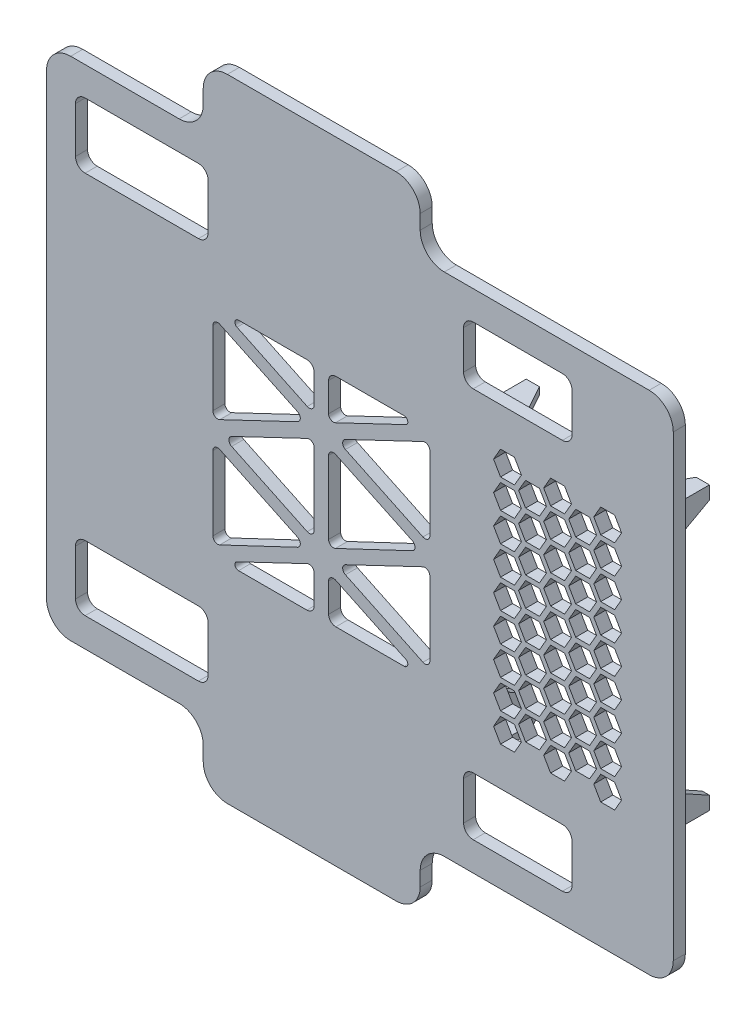
SolidWorks part; units mm, degrees
ref_plane "前视基准面" through (0, 0, 0) normal (0, 0, 1) x (1, 0, 0)
ref_plane "上视基准面" through (0, 0, 0) normal (0, 1, 0) x (1, 0, 0)
ref_plane "右视基准面" through (0, 0, 0) normal (1, 0, 0) x (0, 0, -1)
sketch "草图1" plane through (0, 0, 0) normal (0, 0, 1) x (1, 0, 0)
  line L2 (-130, 95) -> (-130, -95)
  line L3 (-120, -105) -> (-75, -105)
  line L4 (130, 95) -> (130, -95)
  line L5 (126.7518, 102.3765) -> (130, 105) construction
  line L6 (-130, -105) -> (-126.7518, -102.3765) construction
  line L9 (-65, -115) -> (-65, -121)
  line L10 (-55, -131) -> (15, -131)
  line L11 (25, -121) -> (25, -115)
  line L13 (35, -105) -> (120, -105)
  line L14 (126.7518, -102.3765) -> (130, -105) construction
  line L15 (-130, 105) -> (-126.7518, 102.3765) construction
  line L16 (-130, 0) -> (130, 0) construction
  line L17 (35, 105) -> (120, 105)
  line L18 (25, 121) -> (25, 115)
  line L19 (-55, 131) -> (15, 131)
  line L20 (-65, 115) -> (-65, 121)
  line L21 (-120, 105) -> (-75, 105)
  arc A1 (-120, -105) -> (-130, -95) centre (-120, -95) cw
  arc A3 (120, -105) -> (130, -95) centre (120, -95) ccw
  arc A8 (-65, -115) -> (-75, -105) centre (-75, -115) ccw
  arc A9 (25, -115) -> (35, -105) centre (35, -115) cw
  arc A10 (-55, -131) -> (-65, -121) centre (-55, -121) cw
  arc A11 (15, -131) -> (25, -121) centre (15, -121) ccw
  arc A12 (15, 131) -> (25, 121) centre (15, 121) cw
  arc A13 (-55, 131) -> (-65, 121) centre (-55, 121) ccw
  arc A14 (25, 115) -> (35, 105) centre (35, 115) ccw
  arc A15 (-65, 115) -> (-75, 105) centre (-75, 115) cw
  arc A16 (120, 105) -> (130, 95) centre (120, 95) cw
  arc A17 (-120, 105) -> (-130, 95) centre (-120, 95) ccw
  point P0 (0, 0)
  point P40 (25, -105)
  point P45 (25, 105)
  dimension "D2" = 10
  dimension "D3" = 65
  dimension "D4" = 10
  dimension "D5" = 105
  dimension "D7" = 10
  dimension "D8" = 10
  dimension "D10" = 10
  dimension "D12" = 10
  dimension "D13" = 105
  dimension "D18" = 90
  dimension "D19" = 6
extrude "凸台-拉伸1" add sketch "草图1" along normal blind 5
sketch "草图4" plane through (0, 0, 0) normal (0, 0, -1) x (-1, 0, 0)
  line L0 (-44, -47.5) -> (-44, -58.5)
  line L1 (-44, -58.5) -> (-55, -58.5)
  line L2 (-55, -58.5) -> (-55, -55.5)
  line L3 (-55, -55.5) -> (-47, -55.5)
  line L4 (-47, -55.5) -> (-47, -47.5)
  line L5 (-47, -47.5) -> (-44, -47.5)
  line L6 (-130, 0) -> (-25.5592, 0) construction
  line L7 (-130, -95) -> (-130, 95) construction
  line L10 (-130, -95) -> (-130, 95) construction
  dimension "D1" = 11
  dimension "D2" = 11
  dimension "D3" = 3
  dimension "D4" = 3
  dimension "D5" = 75
  dimension "D7" = 55.5
extrude "凸台-拉伸2" add sketch "草图4" along normal blind 20
sketch "草图5" plane through (0, -58.5, 0) normal (0, -1, 0) x (1, 0, 0)
  line L0 (55, -10) -> (49.5, -20)
  line L1 (55, -20) -> (55, 0) construction
  line L2 (55, -20) -> (44, -20) construction
  line L3 (49.5, -20) -> (55, -20)
  line L4 (55, -20) -> (55, -10)
  dimension "D1" = 10
  dimension "D2" = 5.5
extrude "切除-拉伸3" cut sketch "草图5" against normal blind 10
sketch "草图6" plane through (44, 0, 0) normal (-1, 0, 0) x (0, 0, 1)
  line L0 (-20, -53) -> (-10, -47.5)
  line L1 (-20, -58.5) -> (-20, -47.5) construction
  line L2 (-20, -47.5) -> (0, -47.5) construction
  line L3 (-10, -47.5) -> (-20, -47.5)
  line L4 (-20, -47.5) -> (-20, -53)
  dimension "D1" = 10
  dimension "D2" = 5.5
extrude "切除-拉伸4" cut sketch "草图6" against normal blind 10
ref_plane "基准面2" through (82, 0, 0) normal (1, 0, 0) x (0, 0, -1)
mirror "镜向1" about plane through (82, 0, 0) normal (1, 0, 0) of "凸台-拉伸2", "切除-拉伸4", "切除-拉伸3"
mirror "镜向2" about plane through (0, 0, 0) normal (0, 1, 0) of "镜向1"
sketch "草图7" plane through (0, 0, 0) normal (0, 0, -1) x (-1, 0, 0)
  line L4 (-117, -55.5) -> (-109, -55.5) construction
  line L5 (-117, 47.5) -> (-117, 55.5) construction
  line L6 (-117, 55.5) -> (-109, 55.5) construction
  line L7 (-97.013, 36) -> (-99.8997, 41)
  line L8 (-99.8997, 41) -> (-105.6732, 41)
  line L9 (-105.6732, 41) -> (-108.56, 36)
  line L10 (-108.56, 36) -> (-105.6732, 31)
  line L11 (-105.6732, 31) -> (-99.8997, 31)
  line L12 (-99.8997, 31) -> (-97.013, 36)
  line L13 (-82.0019, 36) -> (-102.7865, 36) construction
  line L14 (-79.1151, 31) -> (-76.2284, 36)
  line L15 (-76.2284, 36) -> (-79.1151, 41)
  line L16 (-79.1151, 41) -> (-84.8886, 41)
  line L17 (-84.8886, 41) -> (-87.7754, 36)
  line L18 (-87.7754, 36) -> (-84.8886, 31)
  line L19 (-84.8886, 31) -> (-79.1151, 31)
  line L20 (-97.013, 24) -> (-99.8997, 29)
  line L21 (-98.1677, 30) -> (-95.2809, 25)
  line L22 (-95.2809, 25) -> (-89.5074, 25)
  line L23 (-89.5074, 25) -> (-86.6207, 30)
  line L24 (-86.6207, 30) -> (-89.5074, 35)
  line L25 (-89.5074, 35) -> (-95.2809, 35)
  line L26 (-95.2809, 35) -> (-98.1677, 30)
  line L27 (-89.5074, 37) -> (-86.6207, 42)
  line L28 (-86.6207, 42) -> (-89.5074, 47)
  line L29 (-89.5074, 47) -> (-95.2809, 47)
  line L30 (-95.2809, 47) -> (-98.1677, 42)
  line L31 (-98.1677, 42) -> (-95.2809, 37)
  line L32 (-95.2809, 37) -> (-89.5074, 37)
  line L33 (-84.8886, 43) -> (-79.1151, 43)
  line L34 (-79.1151, 43) -> (-76.2284, 48)
  line L35 (-76.2284, 48) -> (-79.1151, 53)
  line L36 (-79.1151, 53) -> (-84.8886, 53)
  line L37 (-84.8886, 53) -> (-87.7754, 48)
  line L38 (-87.7754, 48) -> (-84.8886, 43)
  line L39 (-99.8997, 43) -> (-97.013, 48)
  line L40 (-97.013, 48) -> (-99.8997, 53)
  line L41 (-99.8997, 53) -> (-105.6732, 53)
  line L42 (-105.6732, 53) -> (-108.56, 48)
  line L43 (-108.56, 48) -> (-105.6732, 43)
  line L44 (-105.6732, 43) -> (-99.8997, 43)
  line L45 (-77.3831, 42) -> (-74.4963, 37)
  line L46 (-74.4963, 37) -> (-68.7228, 37)
  line L47 (-68.7228, 37) -> (-65.8361, 42)
  line L48 (-65.8361, 42) -> (-68.7228, 47)
  line L49 (-68.7228, 47) -> (-74.4963, 47)
  line L50 (-74.4963, 47) -> (-77.3831, 42)
  line L51 (-99.8997, 29) -> (-105.6732, 29)
  line L52 (-105.6732, 29) -> (-108.56, 24)
  line L53 (-108.56, 24) -> (-105.6732, 19)
  line L54 (-105.6732, 19) -> (-99.8997, 19)
  line L55 (-99.8997, 19) -> (-97.013, 24)
  line L56 (-98.1677, 18) -> (-95.2809, 13)
  line L57 (-95.2809, 13) -> (-89.5074, 13)
  line L58 (-89.5074, 13) -> (-86.6207, 18)
  line L59 (-86.6207, 18) -> (-89.5074, 23)
  line L60 (-89.5074, 23) -> (-95.2809, 23)
  line L61 (-95.2809, 23) -> (-98.1677, 18)
  line L62 (-79.1151, 19) -> (-76.2284, 24)
  line L63 (-76.2284, 24) -> (-79.1151, 29)
  line L64 (-79.1151, 29) -> (-84.8886, 29)
  line L65 (-84.8886, 29) -> (-87.7754, 24)
  line L66 (-87.7754, 24) -> (-84.8886, 19)
  line L67 (-84.8886, 19) -> (-79.1151, 19)
  line L68 (-77.3831, 30) -> (-74.4963, 25)
  line L69 (-74.4963, 25) -> (-68.7228, 25)
  line L70 (-68.7228, 25) -> (-65.8361, 30)
  line L71 (-65.8361, 30) -> (-68.7228, 35)
  line L72 (-68.7228, 35) -> (-74.4963, 35)
  line L73 (-74.4963, 35) -> (-77.3831, 30)
  line L74 (-97.013, 12) -> (-99.8997, 17)
  line L75 (-99.8997, 17) -> (-105.6732, 17)
  line L76 (-105.6732, 17) -> (-108.56, 12)
  line L77 (-108.56, 12) -> (-105.6732, 7)
  line L78 (-105.6732, 7) -> (-99.8997, 7)
  line L79 (-99.8997, 7) -> (-97.013, 12)
  line L80 (-98.1677, 6) -> (-95.2809, 1)
  line L81 (-95.2809, 1) -> (-89.5074, 1)
  line L82 (-89.5074, 1) -> (-86.6207, 6)
  line L83 (-86.6207, 6) -> (-89.5074, 11)
  line L84 (-89.5074, 11) -> (-95.2809, 11)
  line L85 (-95.2809, 11) -> (-98.1677, 6)
  line L86 (-79.1151, 7) -> (-76.2284, 12)
  line L87 (-76.2284, 12) -> (-79.1151, 17)
  line L88 (-79.1151, 17) -> (-84.8886, 17)
  line L89 (-84.8886, 17) -> (-87.7754, 12)
  line L90 (-87.7754, 12) -> (-84.8886, 7)
  line L91 (-84.8886, 7) -> (-79.1151, 7)
  line L92 (-77.3831, 18) -> (-74.4963, 13)
  line L93 (-74.4963, 13) -> (-68.7228, 13)
  line L94 (-68.7228, 13) -> (-65.8361, 18)
  line L95 (-65.8361, 18) -> (-68.7228, 23)
  line L96 (-68.7228, 23) -> (-74.4963, 23)
  line L97 (-74.4963, 23) -> (-77.3831, 18)
  line L98 (-97.013, 0) -> (-99.8997, 5)
  line L99 (-99.8997, 5) -> (-105.6732, 5)
  line L100 (-105.6732, 5) -> (-108.56, 0)
  line L101 (-108.56, 0) -> (-105.6732, -5)
  line L102 (-105.6732, -5) -> (-99.8997, -5)
  line L103 (-99.8997, -5) -> (-97.013, 0)
  line L104 (-98.1677, -6) -> (-95.2809, -11)
  line L105 (-95.2809, -11) -> (-89.5074, -11)
  line L106 (-89.5074, -11) -> (-86.6207, -6)
  line L107 (-86.6207, -6) -> (-89.5074, -1)
  line L108 (-89.5074, -1) -> (-95.2809, -1)
  line L109 (-95.2809, -1) -> (-98.1677, -6)
  line L110 (-79.1151, -5) -> (-76.2284, 0)
  line L111 (-76.2284, 0) -> (-79.1151, 5)
  line L112 (-79.1151, 5) -> (-84.8886, 5)
  line L113 (-84.8886, 5) -> (-87.7754, 0)
  line L114 (-87.7754, 0) -> (-84.8886, -5)
  line L115 (-84.8886, -5) -> (-79.1151, -5)
  line L116 (-77.3831, 6) -> (-74.4963, 1)
  line L117 (-74.4963, 1) -> (-68.7228, 1)
  line L118 (-68.7228, 1) -> (-65.8361, 6)
  line L119 (-65.8361, 6) -> (-68.7228, 11)
  line L120 (-68.7228, 11) -> (-74.4963, 11)
  line L121 (-74.4963, 11) -> (-77.3831, 6)
  line L122 (-97.013, -12) -> (-99.8997, -7)
  line L123 (-99.8997, -7) -> (-105.6732, -7)
  line L124 (-105.6732, -7) -> (-108.56, -12)
  line L125 (-108.56, -12) -> (-105.6732, -17)
  line L126 (-105.6732, -17) -> (-99.8997, -17)
  line L127 (-99.8997, -17) -> (-97.013, -12)
  line L128 (-98.1677, -18) -> (-95.2809, -23)
  line L129 (-95.2809, -23) -> (-89.5074, -23)
  line L130 (-89.5074, -23) -> (-86.6207, -18)
  line L131 (-86.6207, -18) -> (-89.5074, -13)
  line L132 (-89.5074, -13) -> (-95.2809, -13)
  line L133 (-95.2809, -13) -> (-98.1677, -18)
  line L134 (-79.1151, -17) -> (-76.2284, -12)
  line L135 (-76.2284, -12) -> (-79.1151, -7)
  line L136 (-79.1151, -7) -> (-84.8886, -7)
  line L137 (-84.8886, -7) -> (-87.7754, -12)
  line L138 (-87.7754, -12) -> (-84.8886, -17)
  line L139 (-84.8886, -17) -> (-79.1151, -17)
  line L140 (-77.3831, -6) -> (-74.4963, -11)
  line L141 (-74.4963, -11) -> (-68.7228, -11)
  line L142 (-68.7228, -11) -> (-65.8361, -6)
  line L143 (-65.8361, -6) -> (-68.7228, -1)
  line L144 (-68.7228, -1) -> (-74.4963, -1)
  line L145 (-74.4963, -1) -> (-77.3831, -6)
  line L146 (-97.013, -24) -> (-99.8997, -19)
  line L147 (-99.8997, -19) -> (-105.6732, -19)
  line L148 (-105.6732, -19) -> (-108.56, -24)
  line L149 (-108.56, -24) -> (-105.6732, -29)
  line L150 (-105.6732, -29) -> (-99.8997, -29)
  line L151 (-99.8997, -29) -> (-97.013, -24)
  line L152 (-98.1677, -30) -> (-95.2809, -35)
  line L153 (-95.2809, -35) -> (-89.5074, -35)
  line L154 (-89.5074, -35) -> (-86.6207, -30)
  line L155 (-86.6207, -30) -> (-89.5074, -25)
  line L156 (-89.5074, -25) -> (-95.2809, -25)
  line L157 (-95.2809, -25) -> (-98.1677, -30)
  line L158 (-79.1151, -29) -> (-76.2284, -24)
  line L159 (-76.2284, -24) -> (-79.1151, -19)
  line L160 (-79.1151, -19) -> (-84.8886, -19)
  line L161 (-84.8886, -19) -> (-87.7754, -24)
  line L162 (-87.7754, -24) -> (-84.8886, -29)
  line L163 (-84.8886, -29) -> (-79.1151, -29)
  line L164 (-77.3831, -18) -> (-74.4963, -23)
  line L165 (-74.4963, -23) -> (-68.7228, -23)
  line L166 (-68.7228, -23) -> (-65.8361, -18)
  line L167 (-65.8361, -18) -> (-68.7228, -13)
  line L168 (-68.7228, -13) -> (-74.4963, -13)
  line L169 (-74.4963, -13) -> (-77.3831, -18)
  line L170 (-97.013, -36) -> (-99.8997, -31)
  line L171 (-99.8997, -31) -> (-105.6732, -31)
  line L172 (-105.6732, -31) -> (-108.56, -36)
  line L173 (-108.56, -36) -> (-105.6732, -41)
  line L174 (-105.6732, -41) -> (-99.8997, -41)
  line L175 (-99.8997, -41) -> (-97.013, -36)
  line L176 (-98.1677, -42) -> (-95.2809, -47)
  line L177 (-95.2809, -47) -> (-89.5074, -47)
  line L178 (-89.5074, -47) -> (-86.6207, -42)
  line L179 (-86.6207, -42) -> (-89.5074, -37)
  line L180 (-89.5074, -37) -> (-95.2809, -37)
  line L181 (-95.2809, -37) -> (-98.1677, -42)
  line L182 (-79.1151, -41) -> (-76.2284, -36)
  line L183 (-76.2284, -36) -> (-79.1151, -31)
  line L184 (-79.1151, -31) -> (-84.8886, -31)
  line L185 (-84.8886, -31) -> (-87.7754, -36)
  line L186 (-87.7754, -36) -> (-84.8886, -41)
  line L187 (-84.8886, -41) -> (-79.1151, -41)
  line L188 (-77.3831, -30) -> (-74.4963, -35)
  line L189 (-74.4963, -35) -> (-68.7228, -35)
  line L190 (-68.7228, -35) -> (-65.8361, -30)
  line L191 (-65.8361, -30) -> (-68.7228, -25)
  line L192 (-68.7228, -25) -> (-74.4963, -25)
  line L193 (-74.4963, -25) -> (-77.3831, -30)
  line L194 (-97.013, -48) -> (-99.8997, -43)
  line L195 (-99.8997, -43) -> (-105.6732, -43)
  line L196 (-105.6732, -43) -> (-108.56, -48)
  line L197 (-108.56, -48) -> (-105.6732, -53)
  line L198 (-105.6732, -53) -> (-99.8997, -53)
  line L199 (-99.8997, -53) -> (-97.013, -48)
  line L206 (-79.1151, -53) -> (-76.2284, -48)
  line L207 (-76.2284, -48) -> (-79.1151, -43)
  line L208 (-79.1151, -43) -> (-84.8886, -43)
  line L209 (-84.8886, -43) -> (-87.7754, -48)
  line L210 (-87.7754, -48) -> (-84.8886, -53)
  line L211 (-84.8886, -53) -> (-79.1151, -53)
  line L212 (-77.3831, -42) -> (-74.4963, -47)
  line L213 (-74.4963, -47) -> (-68.7228, -47)
  line L214 (-68.7228, -47) -> (-65.8361, -42)
  line L215 (-65.8361, -42) -> (-68.7228, -37)
  line L216 (-68.7228, -37) -> (-74.4963, -37)
  line L217 (-74.4963, -37) -> (-77.3831, -42)
  line L218 (-66.9908, 36) -> (-64.104, 31)
  line L219 (-66.9908, 48) -> (-64.104, 43)
  line L220 (-64.104, 43) -> (-58.3305, 43)
  line L221 (-58.3305, 43) -> (-55.4438, 48)
  line L222 (-55.4438, 48) -> (-58.3305, 53)
  line L223 (-58.3305, 53) -> (-64.104, 53)
  line L224 (-64.104, 53) -> (-66.9908, 48)
  line L225 (-64.104, 31) -> (-58.3305, 31)
  line L226 (-58.3305, 31) -> (-55.4438, 36)
  line L227 (-55.4438, 36) -> (-58.3305, 41)
  line L228 (-58.3305, 41) -> (-64.104, 41)
  line L229 (-64.104, 41) -> (-66.9908, 36)
  line L230 (-66.9908, 24) -> (-64.104, 19)
  line L231 (-64.104, 19) -> (-58.3305, 19)
  line L232 (-58.3305, 19) -> (-55.4438, 24)
  line L233 (-55.4438, 24) -> (-58.3305, 29)
  line L234 (-58.3305, 29) -> (-64.104, 29)
  line L235 (-64.104, 29) -> (-66.9908, 24)
  line L236 (-66.9908, 12) -> (-64.104, 7)
  line L237 (-64.104, 7) -> (-58.3305, 7)
  line L238 (-58.3305, 7) -> (-55.4438, 12)
  line L239 (-55.4438, 12) -> (-58.3305, 17)
  line L240 (-58.3305, 17) -> (-64.104, 17)
  line L241 (-64.104, 17) -> (-66.9908, 12)
  line L242 (-66.9908, 0) -> (-64.104, -5)
  line L243 (-64.104, -5) -> (-58.3305, -5)
  line L244 (-58.3305, -5) -> (-55.4438, 0)
  line L245 (-55.4438, 0) -> (-58.3305, 5)
  line L246 (-58.3305, 5) -> (-64.104, 5)
  line L247 (-64.104, 5) -> (-66.9908, 0)
  line L248 (-66.9908, -12) -> (-64.104, -17)
  line L249 (-64.104, -17) -> (-58.3305, -17)
  line L250 (-58.3305, -17) -> (-55.4438, -12)
  line L251 (-55.4438, -12) -> (-58.3305, -7)
  line L252 (-58.3305, -7) -> (-64.104, -7)
  line L253 (-64.104, -7) -> (-66.9908, -12)
  line L254 (-66.9908, -24) -> (-64.104, -29)
  line L255 (-64.104, -29) -> (-58.3305, -29)
  line L256 (-58.3305, -29) -> (-55.4438, -24)
  line L257 (-55.4438, -24) -> (-58.3305, -19)
  line L258 (-58.3305, -19) -> (-64.104, -19)
  line L259 (-64.104, -19) -> (-66.9908, -24)
  line L260 (-66.9908, -36) -> (-64.104, -41)
  line L261 (-64.104, -41) -> (-58.3305, -41)
  line L262 (-58.3305, -41) -> (-55.4438, -36)
  line L263 (-55.4438, -36) -> (-58.3305, -31)
  line L264 (-58.3305, -31) -> (-64.104, -31)
  line L265 (-64.104, -31) -> (-66.9908, -36)
  line L266 (-66.9908, -48) -> (-64.104, -53)
  line L267 (-64.104, -53) -> (-58.3305, -53)
  line L268 (-58.3305, -53) -> (-55.4438, -48)
  line L269 (-55.4438, -48) -> (-58.3305, -43)
  line L270 (-58.3305, -43) -> (-64.104, -43)
  line L271 (-64.104, -43) -> (-66.9908, -48)
  line L272 (-98.1677, -54) -> (-95.2809, -59) [skipped]
  line L273 (-95.2809, -59) -> (-89.5074, -59) [skipped]
  line L274 (-89.5074, -59) -> (-86.6207, -54) [skipped]
  line L275 (-86.6207, -54) -> (-89.5074, -49) [skipped]
  line L276 (-89.5074, -49) -> (-95.2809, -49) [skipped]
  line L277 (-95.2809, -49) -> (-98.1677, -54) [skipped]
  circle A0 centre (-102.7865, 36) radius 5 construction
  circle A1 centre (-82.0019, 36) radius 5 construction
  circle A2 centre (-92.3942, 30) radius 5 construction
  circle A3 centre (-92.3942, 42) radius 5 construction
  circle A4 centre (-82.0019, 48) radius 5 construction
  circle A5 centre (-102.7865, 48) radius 5 construction
  circle A6 centre (-71.6096, 42) radius 5 construction
  circle A7 centre (-61.2173, 48) radius 5 construction
  point P4 (-92.3942, 37)
  dimension "D1" = 2
  dimension "D3" = 10
  dimension "D4" = 10
  dimension "D5" = 2
  dimension "D7" = 10
  dimension "D11" = 10
  dimension "D14" = 10
  dimension "D15" = 10
  dimension "D20" = 10
  dimension "D2" = 2
  dimension "D6" = 2
  dimension "D8" = 2
  dimension "D9" = 2
  dimension "D10" = 2
  dimension "D12" = 2
  dimension "D13" = 2
  dimension "D16" = 2
  dimension "D17" = 2
  dimension "D19" = 2
  dimension "D21" = 9
  dimension "D22" = 2.5
  dimension "D23" = 2.5
  dimension "D24" = 8.44
  dimension "D18" = 8
extrude "切除-拉伸5" cut sketch "草图7" against normal blind 5
sketch "草图8" plane through (0, 0, 0) normal (0, 0, -1) x (-1, 0, 0)
  line L0 (-75.3677, 120) -> (-75.3677, -120)
  line L1 (-100.0285, 77.2863) -> (-100.0285, -77.2863)
  line L2 (-100.0285, 77.2863) -> (-75.3677, 120)
  line L3 (-100.0285, -77.2863) -> (-75.3677, -120)
  line L4 (-37.1297, 0) -> (-146.8562, 0) construction
  dimension "D1" = 30
  dimension "D2" = 30
  dimension "D3" = 120
  dimension "D4" = 120
sketch "草图9" plane through (0, 0, 0) normal (0, 0, -1) x (-1, 0, 0)
  line L0 (148.8518, 0) -> (-37.1297, 0) construction
  line L1 (-29, 41) -> (-29, 4)
  line L2 (-25, -45) -> (13, -45)
  line L3 (61, -41) -> (61, -4)
  line L4 (57, 45) -> (19, 45)
  line L5 (-44, 58.5) -> (-44, 47.5) construction
  line L14 (-29, 41) -> (9.8049, 22.5)
  line L15 (57, 0) -> (19, -18.1163)
  line L16 (130, 95) -> (130, -95) construction
  line L17 (63, 93) -> (118, 93)
  line L18 (63, 93) -> (63, 66)
  line L19 (63, 66) -> (118, 66)
  line L20 (118, 93) -> (118, 66)
  line L21 (75, 105) -> (120, 105) construction
  line L22 (63, -66) -> (118, -66)
  line L23 (118, -93) -> (118, -66)
  line L24 (63, -93) -> (118, -93)
  line L25 (63, -93) -> (63, -66)
  line L26 (-120, 105) -> (-35, 105) construction
  line L27 (-43, 93) -> (-88, 93)
  line L28 (-43, 93) -> (-43, 69)
  line L29 (-43, 69) -> (-88, 69)
  line L30 (-88, 93) -> (-88, 69)
  line L31 (-130, -95) -> (-130, 95) construction
  line L32 (-43, -69) -> (-88, -69)
  line L33 (-88, -93) -> (-88, -69)
  line L34 (-43, -93) -> (-88, -93)
  line L35 (-43, -93) -> (-43, -69)
  line L36 (-25, 45) -> (13, 26.8837)
  line L37 (-25, -45) -> (13, -26.8837)
  line L38 (61, 41) -> (22.0746, 22.5575)
  line L39 (-25.5359, 0) -> (13, -18.258)
  line L40 (57, 45) -> (19, 26.8837)
  line L41 (57, -45) -> (19, -26.8837)
  line L42 (16, 61.4977) -> (16, -60.5731) construction
  line L43 (13, 45) -> (13, 26.8837)
  line L44 (19, 45) -> (19, 26.8837)
  line L45 (13, 18.258) -> (13, -18.258)
  line L46 (9.8049, 22.5) -> (-29, 4)
  line L47 (19, 18.1163) -> (57, 0)
  line L48 (22.0746, 22.5575) -> (61, 4)
  line L49 (13, 18.258) -> (-25.5359, 0)
  line L50 (19, 18.1163) -> (19, -18.1163)
  line L51 (22.0746, -22.5575) -> (61, -41)
  line L52 (9.8049, -22.5) -> (-29, -41)
  line L53 (9.8049, -22.5) -> (-29, -4)
  line L54 (22.0746, -22.5575) -> (61, -4)
  line L55 (13, -26.8837) -> (13, -45)
  line L56 (19, -26.8837) -> (19, -45)
  line L57 (13, 45) -> (-25, 45)
  line L58 (-29, -4) -> (-29, -41)
  line L59 (19, -45) -> (57, -45)
  line L60 (61, 4) -> (61, 41)
  point P55 (62.0817, 45.1185)
  dimension "D1" = 45
  dimension "D2" = 45
  dimension "D3" = 15
  dimension "D4" = 90
  dimension "D7" = 12
  dimension "D8" = 12
  dimension "D9" = 27
  dimension "D10" = 55
  dimension "D11" = 12
  dimension "D12" = 45
  dimension "D13" = 42
  dimension "D14" = 24
  dimension "D21" = 4
  dimension "D22" = 4
  dimension "D23" = 4
  dimension "D24" = 4
  dimension "D26" = 4
  dimension "D27" = 3
  dimension "D28" = 45
extrude "切除-拉伸6" cut sketch "草图9" against normal blind 5 contours L27 L30 L29 L28 | L34 L35 L32 L33 | L25 L24 L23 L22 | L20 L17 L18 L19 | L4 L44 L40 | L48 L60 L38 | L47 L50 L15 | L54 L51 L3 | L56 L59 L41 | L55 L37 L2 | L53 L58 L52 | L45 L49 L39 | L46 L14 L1 | L43 L57 L36 | L57 L36 L43 region at (16.065, 22.5, 0) region at (-0.3333, -38.9612, 0) region at (-48.0249, -22.5192, 0) region at (-31.6667, 38.9612, 0) region at (-31.6667, 0, 0) region at (-90.5, 79.5, 0) region at (-90.5, -79.5, 0) region at (65.5, 81, 0) region at (65.5, -81, 0) region at (-0.3333, 38.9612, 0) region at (-48.0249, 22.5192, 0) region at (-0.1547, 0, 0) region at (-31.6667, -38.9612, 0) region at (16.065, -22.5, 0)
fillet "圆角1" radius 4 16 edges at (-63, -93, 2.5) (-63, -66, 2.5) (-118, -93, 2.5) (-118, -66, 2.5) (-63, 66, 2.5) (-118, 66, 2.5) (-118, 93, 2.5) (-63, 93, 2.5) (43, -93, 2.5) (88, -69, 2.5) (43, -69, 2.5) (88, -93, 2.5) (88, 69, 2.5) (43, 69, 2.5) (43, 93, 2.5) (88, 93, 2.5)
fillet "圆角2" radius 1.5 4 edges at (25, -45, 2.5) (-57, -45, 2.5) (25, 45, 2.5) (-57, 45, 2.5)
fillet "圆角3" radius 2 22 edges at (29, -4, 2.5) (29, 4, 2.5) (-13, -18.258, 2.5) (-61, -41, 2.5) (-61, 4, 2.5) (-13, -26.8837, 2.5) (-13, 18.258, 2.5) (-61, -4, 2.5) (-22.0746, -22.5575, 2.5) (25.5359, 0, 2.5) (-22.0746, 22.5575, 2.5) (-61, 41, 2.5) (-19, 26.8837, 2.5) (-19, -26.8837, 2.5) (-19, -18.1163, 2.5) (29, -41, 2.5) (29, 41, 2.5) (-57, 0, 2.5) (-9.8049, -22.5, 2.5) (-13, 26.8837, 2.5) (-9.8049, 22.5, 2.5) (-19, 18.1163, 2.5)
fillet "圆角4" radius 3 4 edges at (-13, -45, 2.5) (-13, 45, 2.5) (-19, -45, 2.5) (-19, 45, 2.5)
equation "\"45、\"=43.7672"
